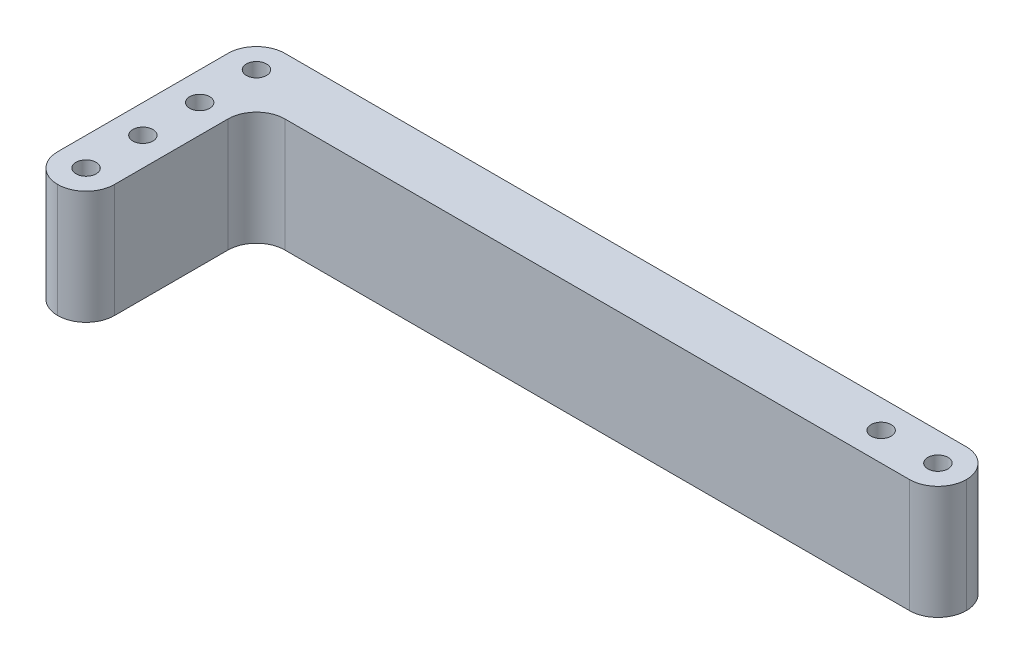
SolidWorks part; units mm, degrees
ref_plane "Front Plane" through (0, 0, 0) normal (0, 0, 1) x (1, 0, 0)
ref_plane "Top Plane" through (0, 0, 0) normal (0, 1, 0) x (1, 0, 0)
ref_plane "Right Plane" through (0, 0, 0) normal (1, 0, 0) x (0, 0, -1)
sketch "Sketch1" plane through (0, 0, 0) normal (0, 1, 0) x (1, 0, 0)
  line L0 (0, 0) -> (0, 38.1) construction
  line L1 (0, 38.1) -> (152.4, 38.1) construction
  line L2 (158.75, 44.45) -> (158.75, 31.75)
  line L3 (158.75, 31.75) -> (6.35, 31.75)
  line L4 (6.35, 31.75) -> (6.35, -6.35)
  line L5 (6.35, -6.35) -> (-6.35, -6.35)
  line L6 (-6.35, -6.35) -> (-6.35, 31.75)
  line L7 (-6.35, 31.75) -> (-19.05, 31.75)
  line L8 (-19.05, 31.75) -> (-19.05, 44.45)
  line L9 (-19.05, 44.45) -> (158.75, 44.45)
  circle A0 centre (0, 38.1) radius 2.25
  circle A1 centre (152.4, 38.1) radius 2.25
  circle A2 centre (139.7, 38.1) radius 2.25
  circle A3 centre (0, 25.4) radius 2.25
  circle A4 centre (0, 12.7) radius 2.25
  circle A5 centre (0, 0) radius 2.25
  point P16 (0, 0)
  dimension "D3" = 4.5
  dimension "D1" = 38.1
  dimension "D2" = 152.4
  dimension "D4" = 12.7
  dimension "D6" = 12.7
  dimension "D7" = 12.7
  dimension "D8" = 12.7
  dimension "D9" = 6.35
  dimension "D10" = 6.35
  dimension "D5" = 4
extrude "Boss-Extrude1" add sketch "Sketch1" along normal blind 25.4
sketch "Sketch2" plane through (0, 0, -31.75) normal (0, 0, 1) x (1, 0, 0)
  line L0 (-19.05, 0) -> (-6.35, 0) construction
  line L1 (-19.05, 25.4) -> (-19.05, 0) construction
  line L5 (-6.35, 25.4) -> (-6.35, 0) construction
  line L6 (-19.05, 25.4) -> (-6.35, 25.4)
  line L7 (-19.05, 25.4) -> (-19.05, 12.7)
  line L8 (-19.05, 12.7) -> (-6.35, 12.7)
  line L9 (-6.35, 25.4) -> (-6.35, 12.7)
  circle A0 centre (-12.7, 6.35) radius 2.25
  dimension "D1" = 4.5
  dimension "D2" = 6.35
  dimension "D3" = 6.35
  dimension "D4" = 12.7
extrude "Cut-Extrude1" cut sketch "Sketch2" against normal blind 12.7
fillet "Fillet1" radius 6.35 8 edges at (158.75, 12.7, -44.45) (158.75, 12.7, -31.75) (6.35, 12.7, 6.35) (-6.35, 12.7, 6.35) (-19.05, 0, -38.1) (-6.35, 19.05, -44.45) (-19.05, 12.7, -38.1) (6.35, 12.7, -31.75)
fillet "Fillet2" radius 6.35 2 edges at (-4.4901, 12.7, -42.5901) (-6.35, 12.7, -34.925)
